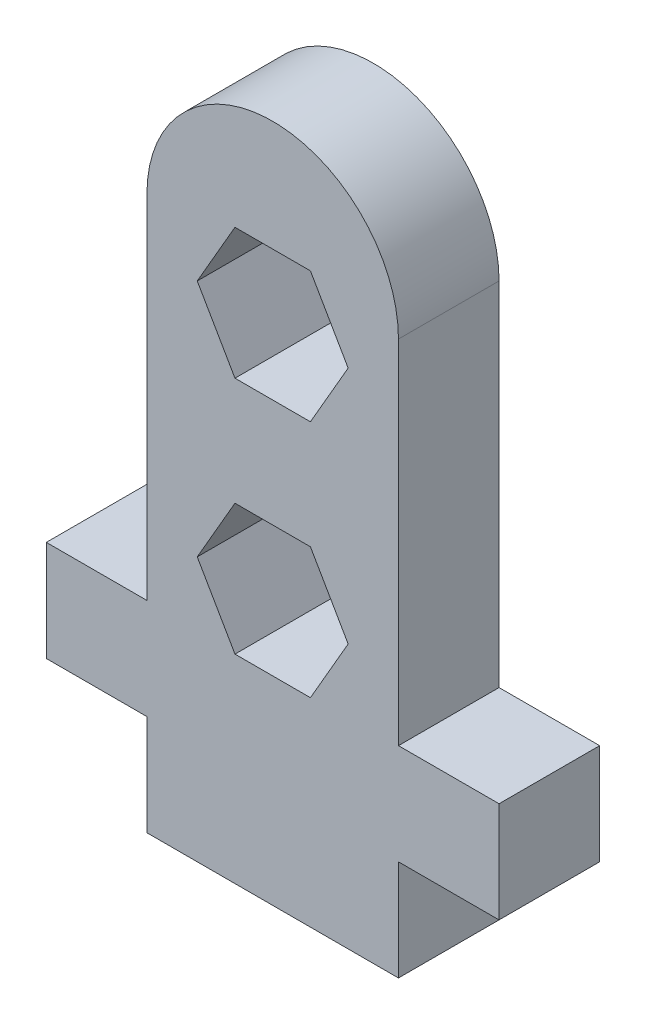
SolidWorks part; units mm, degrees
ref_plane "Front Plane" through (0, 0, 0) normal (0, 0, 1) x (1, 0, 0)
ref_plane "Top Plane" through (0, 0, 0) normal (0, 1, 0) x (1, 0, 0)
ref_plane "Right Plane" through (0, 0, 0) normal (1, 0, 0) x (0, 0, -1)
sketch "Sketch1" plane through (0, 0, 0) normal (0, 0, 1) x (1, 0, 0)
  line L0 (0, 0) -> (10, 0)
  line L1 (0, 0) -> (0, 4)
  line L2 (0, 4) -> (-4, 4)
  line L3 (3.5, 17.4019) -> (6.5, 17.4019)
  line L4 (-4, 4) -> (-4, 8)
  line L5 (-4, 8) -> (0, 8)
  line L6 (0, 8) -> (0, 22)
  line L7 (10, 8) -> (10, 22)
  line L8 (10, 0) -> (10, 4)
  line L9 (14, 8) -> (10, 8)
  line L10 (14, 4) -> (14, 8)
  line L11 (10, 4) -> (14, 4)
  line L12 (3.5, 22.5981) -> (2, 20)
  line L13 (8, 10.5) -> (6.5, 13.0981)
  line L14 (6.5, 13.0981) -> (3.5, 13.0981)
  line L15 (3.5, 13.0981) -> (2, 10.5)
  line L16 (2, 10.5) -> (3.5, 7.9019)
  line L17 (3.5, 7.9019) -> (6.5, 7.9019)
  line L18 (6.5, 7.9019) -> (8, 10.5)
  line L19 (2, 20) -> (3.5, 17.4019)
  line L22 (6.5, 17.4019) -> (8, 20)
  line L23 (8, 20) -> (6.5, 22.5981)
  line L24 (6.5, 22.5981) -> (3.5, 22.5981)
  arc A0 (10, 22) -> (0, 22) centre (5, 22) ccw
  dimension "D5" = 14
  dimension "D6" = 5
  dimension "D1" = 4
  dimension "D2" = 4
  dimension "D3" = 4
  dimension "D4" = 10
  dimension "D7" = 9.5
extrude "Boss-Extrude1" add sketch "Sketch1" along normal blind 4
